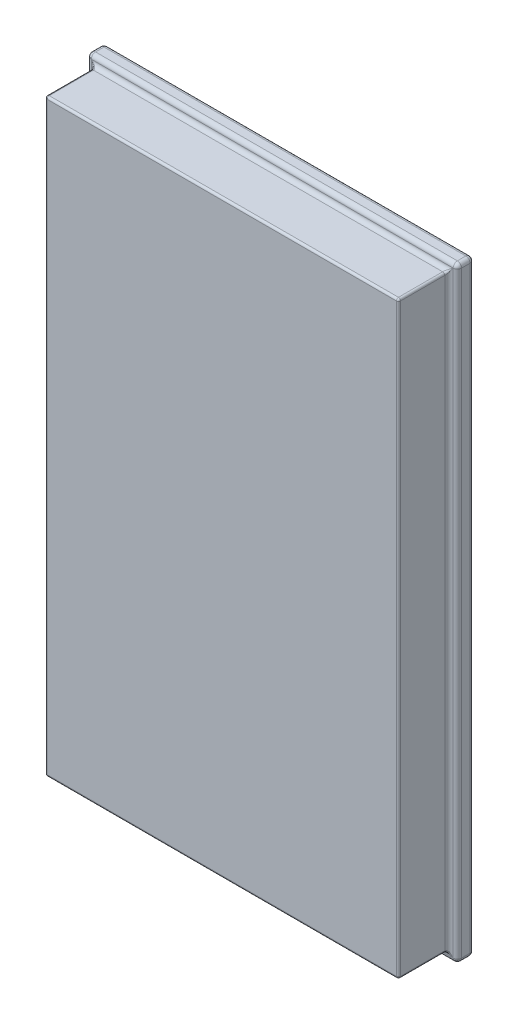
SolidWorks part; units mm, degrees
ref_plane "Front Plane" through (0, 0, 0) normal (1, 0, 0) x (0, 1, 0)
ref_plane "Top Plane" through (0, 0, 0) normal (0, 0, 1) x (0, 1, 0)
ref_plane "Right Plane" through (0, 0, 0) normal (0, 1, 0) x (-1, 0, 0)
sketch "Sketch1" plane through (0, 0, 0) normal (0, 0, 1) x (0, 1, 0)
  line L1 (-228.6, -139.7) -> (228.6, -139.7)
  line L2 (-228.6, -139.7) -> (-228.6, 139.7)
  line L3 (-228.6, 139.7) -> (228.6, 139.7)
  line L4 (228.6, -139.7) -> (228.6, 139.7)
  line L5 (-228.6, -139.7) -> (228.6, 139.7) construction
  line L6 (-228.6, 139.7) -> (228.6, -139.7) construction
  point P0 (0, 0)
extrude "Boss-Extrude1" add sketch "Sketch1" along normal blind 12.7
sketch "Sketch2" plane through (0, 0, 0) normal (0, 0, 1) x (0, 1, 0)
  line L1 (-222.25, -133.35) -> (222.25, -133.35)
  line L2 (-222.25, -133.35) -> (-222.25, 133.35)
  line L3 (-222.25, 133.35) -> (222.25, 133.35)
  line L4 (222.25, -133.35) -> (222.25, 133.35)
  line L5 (-222.25, -133.35) -> (222.25, 133.35) construction
  line L6 (-222.25, 133.35) -> (222.25, -133.35) construction
  point P0 (0, 0)
extrude "Boss-Extrude2" add sketch "Sketch2" along normal blind 38.1 from offset 12.7
fillet "Fillet1" radius 3.175 16 edges at (-139.7, 228.6, 6.35) (-139.7, -228.6, 6.35) (139.7, -228.6, 6.35) (139.7, 228.6, 6.35) (-139.7, 0, 0) (0, -228.6, 0) (139.7, 0, 0) (0, 228.6, 0) (-133.35, 0, 12.7) (0, -222.25, 12.7) (133.35, 0, 12.7) (0, 222.25, 12.7) (139.7, 0, 12.7) (0, -228.6, 12.7) (-139.7, 0, 12.7) (0, 228.6, 12.7) tangent propagation no
fillet "Fillet2" radius 1.5875 8 edges at (-133.35, 222.25, 33.3375) (-133.35, -222.25, 33.3375) (133.35, 222.25, 33.3375) (133.35, -222.25, 33.3375) (133.35, 0, 50.8) (0, -222.25, 50.8) (-133.35, 0, 50.8) (0, 222.25, 50.8) tangent propagation no
